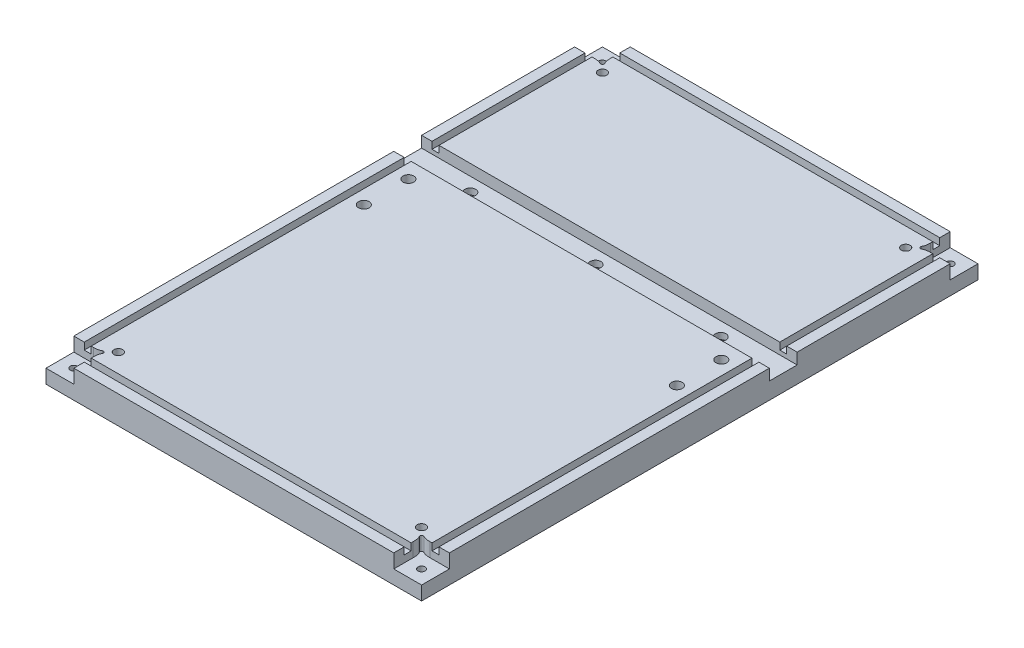
SolidWorks part; units mm, degrees
ref_plane "Front Plane" through (0, 0, 0) normal (0, 0, 1) x (1, 0, 0)
ref_plane "Top Plane" through (0, 0, 0) normal (0, 1, 0) x (1, 0, 0)
ref_plane "Right Plane" through (0, 0, 0) normal (1, 0, 0) x (0, 0, -1)
sketch "Base" plane through (0, 0, 0) normal (0, 1, 0) x (1, 0, 0)
  line L1 (-201.9764, 133.7508) -> (140.9236, 133.7508)
  line L2 (-201.9764, 133.7508) -> (-201.9764, -374.2492)
  line L3 (-201.9764, -374.2492) -> (140.9236, -374.2492)
  line L4 (140.9236, 133.7508) -> (140.9236, -374.2492)
  dimension "D1" = 342.9
  dimension "D2" = 508
extrude "Boss-Extrude1" add sketch "Base" along normal blind 25.4
sketch "Sketch2" plane through (0, 25.4, 0) normal (0, 1, 0) x (1, 0, 0)
  line L1 (172.6736, -31.3492) -> (-233.7264, -31.3492)
  line L2 (172.6736, -31.3492) -> (172.6736, -56.7492)
  line L3 (172.6736, -56.7492) -> (-233.7264, -56.7492)
  line L4 (-233.7264, -31.3492) -> (-233.7264, -56.7492)
  line L6 (140.9236, 133.7508) -> (-201.9764, 133.7508) construction
  line L9 (-30.5264, 133.7508) -> (-30.5264, -374.2492) construction
  line L10 (-201.9764, -374.2492) -> (140.9236, -374.2492) construction
  point P6 (-30.5264, -31.3492)
  dimension "D1" = 317.5
  dimension "D2" = 25.4
  dimension "D3" = 406.4
extrude "Cut-Extrude1" cut sketch "Sketch2" against normal blind 10.16
hole_wizard "CBORE for 3/8 Socket Head Cap Screw4" positions "3DSketch1" profile "Sketch3" counterbore size "3/8" standard "ANSI Inch" end condition up to next
sketch3d "3DSketch1"
  line L3 (-201.9764, 0, -133.7508) -> (-201.9764, 0, 374.2492) construction
  point P0 (83.7736, 0, 44.0492)
  point P2 (-30.5264, 0, 44.0492)
  point P4 (-144.8264, 0, 44.0492)
  dimension "D1" = 12.7
  dimension "D2" = 12.7
  dimension "D3" = 12.7
  dimension "D4" = 171.45
  dimension "D5" = 114.3
  dimension "D6" = 114.3
sketch "Sketch3" plane through (83.7736, 0, 44.0492) normal (1, 0, 0) x (0, 0, -1)
  line L0 (0, 0) -> (0, 15.24)
  line L1 (0, 15.24) -> (4.9022, 15.24)
  line L3 (4.9022, 15.24) -> (4.9022, 9.525)
  line L4 (4.9022, 9.525) -> (7.9375, 9.525)
  line L5 (7.9375, 9.525) -> (7.9375, 0)
  line L7 (7.9375, 0) -> (0, 0)
  line L11 (0, -6.35) -> (0, 107.95) construction
  dimension "Thru Hole Dia." = 9.8044
  dimension "Thru Hole Depth" = 15.24
  dimension "C'Bore Dia." = 15.875
  dimension "C'Bore Depth" = 9.525
hole_wizard "CBORE for 3/8 Socket Head Cap Screw3" positions "Sketch4" profile "Sketch6" counterbore size "3/8" standard "ANSI Inch" end condition up to next
sketch "Sketch4" plane through (0, 0, 0) normal (0, -1, 0) x (-1, 0, 0)
  line L0 (201.9764, -56.7492) -> (-140.9236, -56.7492) construction
  line L1 (-140.9236, -374.2492) -> (-140.9236, 133.7508) construction
  line L3 (201.9764, 133.7508) -> (201.9764, -374.2492) construction
  point P0 (-112.3486, -71.9892)
  point P2 (-112.3486, -112.6292)
  point P4 (173.4014, -71.9892)
  point P6 (173.4014, -112.6292)
  dimension "D1" = 15.24
  dimension "D2" = 28.575
  dimension "D3" = 28.575
  dimension "D4" = 40.64
  dimension "D5" = 15.24
  dimension "D6" = 28.575
  dimension "D7" = 40.64
  dimension "D8" = 28.575
sketch "Sketch6" plane through (112.3486, 0, 71.9892) normal (1, 0, 0) x (0, 0, -1)
  line L0 (0, 0) -> (0, 25.4)
  line L1 (0, 25.4) -> (4.9022, 25.4)
  line L3 (4.9022, 25.4) -> (4.9022, 15.24)
  line L4 (4.9022, 15.24) -> (7.9375, 15.24)
  line L5 (7.9375, 15.24) -> (7.9375, 0)
  line L7 (7.9375, 0) -> (0, 0)
  line L11 (0, -6.35) -> (0, 107.95) construction
  dimension "Thru Hole Dia." = 9.8044
  dimension "Thru Hole Depth" = 25.4
  dimension "C'Bore Dia." = 15.875
  dimension "C'Bore Depth" = 15.24
hole_wizard "CBORE for 1/4 Socket Head Cap Screw1" positions "3DSketch2" profile "Sketch9" counterbore size "1/4" standard "ANSI Inch" end condition up to next
sketch3d "3DSketch2"
  line L0 (140.9236, 0, -133.7508) -> (-201.9764, 0, -133.7508) construction
  line L1 (140.9236, 0, 374.2492) -> (140.9236, 0, -133.7508) construction
  line L2 (-201.9764, 0, -133.7508) -> (-201.9764, 0, 374.2492) construction
  line L3 (-201.9764, 0, 374.2492) -> (140.9236, 0, 374.2492) construction
  point P0 (128.2236, 0, 361.5492)
  point P2 (-189.2764, 0, 361.5492)
  point P4 (-189.2764, 0, -121.0508)
  point P6 (128.2236, 0, -121.0508)
  dimension "D1" = 12.7
  dimension "D2" = 12.7
  dimension "D3" = 12.7
  dimension "D4" = 12.7
  dimension "D5" = 12.7
  dimension "D6" = 12.7
  dimension "D7" = 12.7
  dimension "D8" = 12.7
sketch "Sketch9" plane through (128.2236, 0, 361.5492) normal (1, 0, 0) x (0, 0, -1)
  line L0 (0, 0) -> (0, 25.4)
  line L1 (0, 25.4) -> (3.2639, 25.4)
  line L3 (3.2639, 25.4) -> (3.2639, 6.35)
  line L4 (3.2639, 6.35) -> (5.5562, 6.35)
  line L5 (5.5562, 6.35) -> (5.5562, 0)
  line L7 (5.5562, 0) -> (0, 0)
  line L11 (0, -6.35) -> (0, 107.95) construction
  dimension "Thru Hole Dia." = 6.5278
  dimension "Thru Hole Depth" = 25.4
  dimension "C'Bore Dia." = 11.1125
  dimension "C'Bore Depth" = 6.35
sketch "Sketch8" plane through (0, 25.4, 0) normal (0, 1, 0) x (1, 0, 0)
  line L0 (116.3173, -347.4744) -> (115.5236, -348.8492) construction
  line L1 (140.9236, -374.2492) -> (115.5236, -374.2492)
  line L2 (140.9236, -374.2492) -> (140.9236, -348.8492)
  line L3 (140.9236, -348.8492) -> (123.1436, -348.8492)
  line L4 (115.5236, -374.2492) -> (115.5236, -356.4692)
  line L5 (-201.9764, -374.2492) -> (-176.5764, -374.2492)
  line L6 (-201.9764, -374.2492) -> (-201.9764, -348.8492)
  line L7 (-201.9764, -348.8492) -> (-184.1964, -348.8492)
  line L8 (-176.5764, -374.2492) -> (-176.5764, -356.4692)
  line L9 (-201.9764, 133.7508) -> (-176.5764, 133.7508)
  line L10 (-201.9764, 133.7508) -> (-201.9764, 108.3508)
  line L11 (-201.9764, 108.3508) -> (-184.1964, 108.3508)
  line L12 (-176.5764, 133.7508) -> (-176.5764, 115.9708)
  line L13 (140.9236, 133.7508) -> (115.5236, 133.7508)
  line L14 (140.9236, 133.7508) -> (140.9236, 108.3508)
  line L15 (140.9236, 108.3508) -> (123.1436, 108.3508)
  line L16 (115.5236, 133.7508) -> (115.5236, 115.9708)
  line L17 (115.5236, -348.8492) -> (123.1436, -348.8492) construction
  line L18 (115.5236, -356.4692) -> (115.5236, -348.8492) construction
  line L19 (115.5236, -348.8492) -> (114.1488, -349.6429) construction
  line L20 (115.5236, 108.3508) -> (116.3173, 106.976) construction
  line L21 (115.5236, 108.3508) -> (114.1488, 109.1446) construction
  line L22 (-176.5764, 108.3508) -> (-175.2016, 109.1446) construction
  line L23 (-176.5764, 108.3508) -> (-177.3702, 106.976) construction
  line L24 (-176.5764, -348.8492) -> (-175.2016, -349.6429) construction
  line L25 (-176.5764, -348.8492) -> (-177.3702, -347.4744) construction
  arc A0 (116.3173, -347.4744) -> (114.1488, -349.6429) centre (115.5236, -348.8492) ccw
  arc A1 (114.1488, 109.1446) -> (116.3173, 106.976) centre (115.5236, 108.3508) ccw
  arc A2 (-177.3702, 106.976) -> (-175.2016, 109.1446) centre (-176.5764, 108.3508) ccw
  arc A3 (-175.2016, -349.6429) -> (-177.3702, -347.4744) centre (-176.5764, -348.8492) ccw
  spline S0 degree 3 poles (123.1436, -348.8492) (120.8225, -348.8492) (118.3275, -348.6349) (116.3173, -347.4744) knots 0 0 0 0 1 1 1 1
  spline S1 degree 3 poles (115.5236, -356.4692) (115.5236, -353.9168) (115.3093, -351.6531) (114.1488, -349.6429) knots 0 0 0 0 1 1 1 1
  spline S2 degree 3 poles (123.1436, 108.3508) (120.8225, 108.3508) (118.3275, 108.1366) (116.3173, 106.976) knots 0 0 0 0 1 1 1 1
  spline S3 degree 3 poles (114.1488, 109.1446) (115.3093, 111.1547) (115.5236, 113.6497) (115.5236, 115.9708) knots 0 0 0 0 1 1 1 1
  spline S4 degree 3 poles (-176.5764, 115.9708) (-176.5764, 113.4184) (-176.3621, 111.1547) (-175.2016, 109.1446) knots 0 0 0 0 1 1 1 1
  spline S5 degree 3 poles (-177.3702, 106.976) (-179.3803, 108.1366) (-181.8753, 108.3508) (-184.1964, 108.3508) knots 0 0 0 0 1 1 1 1
  spline S6 degree 3 poles (-175.2016, -349.6429) (-176.7942, -352.4013) (-176.5764, -354.9687) (-176.5764, -356.4692) knots 0 0 0 0 1 1 1 1
  spline S7 degree 3 poles (-177.3702, -347.4744) (-180.1285, -349.0669) (-182.696, -348.8492) (-184.1964, -348.8492) knots 0 0 0 0 1 1 1 1
  point P23 (117.1111, -348.8492)
  point P27 (115.5236, -350.4367)
  dimension "D9" = 7.62
  dimension "D10" = 1.5875
  dimension "D15" = 60
  dimension "D16" = 1.5875
  dimension "D20" = 3.175
  dimension "D25" = 60
  dimension "D28" = 3.175
  dimension "D2" = 25.4
  dimension "D3" = 25.4
  dimension "D4" = 25.4
  dimension "D5" = 25.4
  dimension "D6" = 25.4
  dimension "D7" = 25.4
  dimension "D8" = 25.4
  dimension "D11" = 7.62
  dimension "D12" = 25.4
  dimension "D13" = 60
  dimension "D14" = 60
  dimension "D17" = 60
  dimension "D18" = 7.62
  dimension "D19" = 7.62
  dimension "D21" = 60
  dimension "D22" = 60
  dimension "D23" = 7.62
  dimension "D24" = 7.62
  dimension "D26" = 60
  dimension "D27" = 7.62
  dimension "D29" = 7.62
extrude "Cut-Extrude3" cut sketch "Sketch8" against normal blind 12.7
sketch "Sketch10" plane through (0, 25.4, 0) normal (0, 1, 0) x (1, 0, 0)
  line L1 (125.0486, 108.3508) -> (131.3986, 108.3508)
  line L2 (125.0486, 108.3508) -> (125.0486, -348.8492)
  line L3 (125.0486, -348.8492) -> (131.3986, -348.8492)
  line L4 (131.3986, 108.3508) -> (131.3986, -348.8492)
  line L5 (140.9236, -348.8492) -> (140.9236, -56.7492) construction
  line L8 (-201.9764, 108.3508) -> (-201.9764, -31.3492) construction
  line L9 (-192.4514, 108.3508) -> (-186.1014, 108.3508)
  line L10 (-192.4514, 108.3508) -> (-192.4514, -348.8492)
  line L11 (-192.4514, -348.8492) -> (-186.1014, -348.8492)
  line L12 (-186.1014, 108.3508) -> (-186.1014, -348.8492)
  line L13 (-184.1964, -348.8492) -> (-201.9764, -348.8492) construction
  line L14 (-201.9764, 108.3508) -> (-184.1964, 108.3508) construction
  line L15 (123.1436, 108.3508) -> (140.9236, 108.3508) construction
  line L16 (140.9236, -348.8492) -> (123.1436, -348.8492) construction
  line L17 (-176.5764, 115.9708) -> (-176.5764, 133.7508) construction
  line L18 (-176.5764, 124.2258) -> (115.5236, 124.2258)
  line L19 (-176.5764, 124.2258) -> (-176.5764, 117.8758)
  line L20 (-176.5764, 117.8758) -> (115.5236, 117.8758)
  line L21 (115.5236, 124.2258) -> (115.5236, 117.8758)
  line L22 (115.5236, 133.7508) -> (115.5236, 115.9708) construction
  line L23 (115.5236, 133.7508) -> (-176.5764, 133.7508) construction
  line L24 (-176.5764, -374.2492) -> (-176.5764, -356.4692) construction
  line L25 (-176.5764, -358.3742) -> (115.5236, -358.3742)
  line L26 (-176.5764, -358.3742) -> (-176.5764, -364.7242)
  line L27 (-176.5764, -364.7242) -> (115.5236, -364.7242)
  line L28 (115.5236, -358.3742) -> (115.5236, -364.7242)
  line L29 (115.5236, -356.4692) -> (115.5236, -374.2492) construction
  line L30 (-176.5764, -374.2492) -> (115.5236, -374.2492) construction
  dimension "D1" = 6.35
  dimension "D2" = 6.35
  dimension "D3" = 9.525
  dimension "D4" = 9.525
  dimension "D5" = 6.35
  dimension "D6" = 9.525
  dimension "D7" = 9.525
  dimension "D8" = 6.35
extrude "Cut-Extrude4" cut sketch "Sketch10" against normal blind 6.35
hole_wizard "3/8-16 Tapped Hole2" positions "Sketch17" profile "Sketch18" tap size "3/8-16" standard "ANSI Inch" end condition up to next
sketch "Sketch17" plane through (0, 0, 0) normal (0, -1, 0) x (-1, 0, 0)
  line L0 (-140.9236, 133.7508) -> (201.9764, 133.7508) construction
  line L1 (-140.9236, -374.2492) -> (-140.9236, 133.7508) construction
  line L2 (201.9764, 133.7508) -> (201.9764, -374.2492) construction
  line L3 (201.9764, -374.2492) -> (-140.9236, -374.2492) construction
  point P0 (-107.9036, -341.2292)
  point P2 (168.9564, -341.2292)
  point P4 (168.9564, 100.7308)
  point P6 (-107.9036, 100.7308)
  dimension "D1" = 33.02
  dimension "D2" = 33.02
  dimension "D3" = 33.02
  dimension "D4" = 33.02
  dimension "D5" = 33.02
  dimension "D6" = 33.02
  dimension "D7" = 33.02
  dimension "D8" = 33.02
sketch "Sketch18" plane through (107.9036, 0, 341.2292) normal (1, 0, 0) x (0, 0, -1)
  line L0 (0, 0) -> (0, 25.4)
  line L1 (0, 25.4) -> (3.9687, 25.4)
  line L2 (3.9687, 25.4) -> (3.9687, 0)
  line L5 (3.9687, 0) -> (0, 0)
  line L11 (0, -6.35) -> (0, 107.95) construction
  dimension "Thru Tap Drill Dia." = 7.9375
  dimension "Thru Tap Drill Depth" = 25.4
cosmetic thread "Hole Thread5" parameters "D2"=9.525
cosmetic thread "Hole Thread6" parameters "D2"=9.525
cosmetic thread "Hole Thread7" parameters "D2"=9.525
cosmetic thread "Hole Thread8" parameters "D2"=9.525
sketch "Sketch19" plane through (0, 0, 0) normal (0, -1, 0) x (1, 0, 0)
  circle A0 centre (-168.9564, -100.7308) radius 9.525
  circle A1 centre (-168.9564, 341.2292) radius 9.525
  circle A2 centre (107.9036, 341.2292) radius 9.525
  circle A3 centre (108.2173, -100.7308) radius 9.525
  dimension "D1" = 19.05
  dimension "D2" = 19.05
  dimension "D3" = 19.05
  dimension "D4" = 19.05
extrude "Cut-Extrude5" cut sketch "Sketch19" against normal blind 1.27
